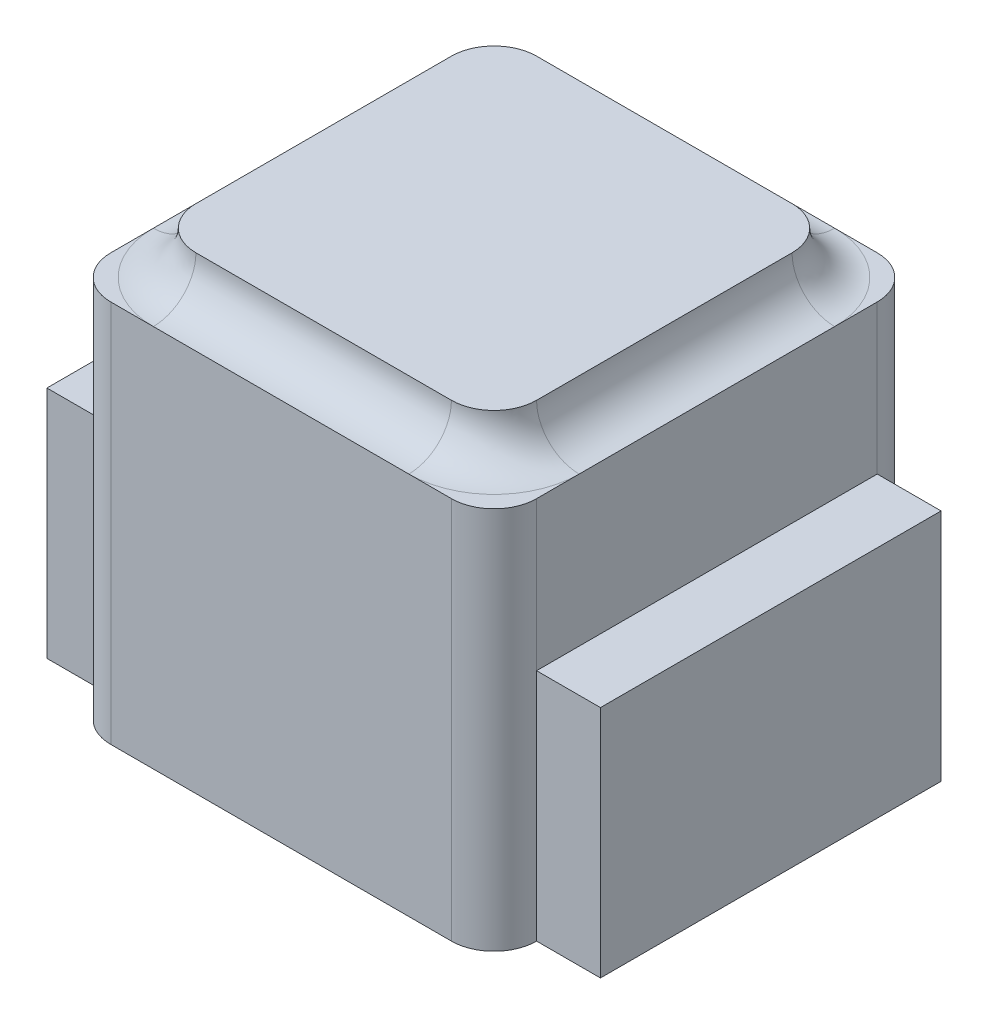
SolidWorks part; units mm, degrees
ref_plane "Front Plane" through (0, 0, 0) normal (0, 0, 1) x (1, 0, 0)
ref_plane "Top Plane" through (0, 0, 0) normal (0, 1, 0) x (1, 0, 0)
ref_plane "Right Plane" through (0, 0, 0) normal (1, 0, 0) x (0, 0, -1)
sketch "Sketch1" plane through (0, 0, 0) normal (0, 1, 0) x (1, 0, 0)
  line L1 (-4, -5) -> (4, -5)
  line L2 (-5, -4) -> (-5, 4)
  line L3 (-4, 5) -> (4, 5)
  line L4 (5, -4) -> (5, 4)
  line L5 (-5, -5) -> (5, 5) construction
  line L6 (-5, 5) -> (5, -5) construction
  arc A0 (4, 5) -> (5, 4) centre (4, 4) cw
  arc A1 (4, -5) -> (5, -4) centre (4, -4) ccw
  arc A2 (-4, -5) -> (-5, -4) centre (-4, -4) cw
  arc A3 (-5, 4) -> (-4, 5) centre (-4, 4) cw
  point P0 (0, 0)
  dimension "D3" = 1
  dimension "D1" = 10
  dimension "D2" = 10
extrude "Boss-Extrude1" add sketch "Sketch1" along normal blind 10
sketch "Sketch2" plane through (0, 0, 0) normal (0, 1, 0) x (1, 0, 0)
  line L1 (-6.5, -4) -> (6.5, -4)
  line L2 (-6.5, -4) -> (-6.5, 4)
  line L3 (-6.5, 4) -> (6.5, 4)
  line L4 (6.5, -4) -> (6.5, 4)
  line L5 (-6.5, -4) -> (6.5, 4) construction
  line L6 (-6.5, 4) -> (6.5, -4) construction
  point P0 (0, 0)
  dimension "D1" = 8
  dimension "D2" = 13
extrude "Boss-Extrude2" add sketch "Sketch2" along normal blind 5.5
sketch "Sketch3" plane through (0, 0, 0) normal (0, -1, 0) x (1, 0, 0)
  line L4 (-3.5, -3.5) -> (3.5, -3.5)
  line L5 (-3.5, -3.5) -> (-3.5, 3.5)
  line L6 (-3.5, 3.5) -> (3.5, 3.5)
  line L7 (3.5, -3.5) -> (3.5, 3.5)
  line L8 (-3.5, -3.5) -> (3.5, 3.5) construction
  line L9 (-3.5, 3.5) -> (3.5, -3.5) construction
  circle A0 centre (0, 0) radius 1.75
  dimension "D1" = 3.5
  dimension "D2" = 1.5
  dimension "D3" = 1.5
extrude "Cut-Extrude1" cut sketch "Sketch3" against normal blind 8
sketch "Sketch4" plane through (-3.5, 0, 0) normal (1, 0, 0) x (0, 0, -1)
  line L0 (-3.5, 0) -> (3.5, 0) construction
  line L1 (0.5, 0) -> (-0.5, 0)
  line L2 (0.5, 0) -> (0.5, 2)
  line L3 (0.5, 2) -> (-0.5, 2)
  line L4 (-0.5, 0) -> (-0.5, 2)
  line L5 (0.5, 0) -> (-0.5, 2) construction
  line L6 (0.5, 2) -> (-0.5, 0) construction
  point P0 (0, 1)
  point P11 (0, 0)
  dimension "D1" = 2
  dimension "D2" = 1
extrude "Boss-Extrude3" add sketch "Sketch4" along normal blind 7
sketch "Sketch5" plane through (0, 10, 0) normal (0, 1, 0) x (1, 0, 0)
  line L0 (-4, -5) -> (4, -5) construction
  line L1 (4, 4) -> (-4, 4)
  line L2 (4, 4) -> (4, -4)
  line L3 (4, -4) -> (-4, -4)
  line L4 (-4, 4) -> (-4, -4)
  line L5 (4, 4) -> (-4, -4) construction
  line L6 (4, -4) -> (-4, 4) construction
  line L7 (5, 5) -> (-5, 5)
  line L8 (5, 5) -> (5, -5)
  line L9 (5, -5) -> (-5, -5)
  line L10 (-5, 5) -> (-5, -5)
  line L11 (5, 5) -> (-5, -5) construction
  line L12 (5, -5) -> (-5, 5) construction
  line L13 (-5, 4) -> (-5, -4) construction
  point P0 (0, 0)
  point P6 (0, 0)
  dimension "D1" = 1
  dimension "D2" = 1
extrude "Cut-Extrude2" cut sketch "Sketch5" against normal blind 1
fillet "Fillet1" radius 1 4 edges at (4, 9, 0) (0, 9, 4) (-4, 9, 0) (0, 9, -4)
